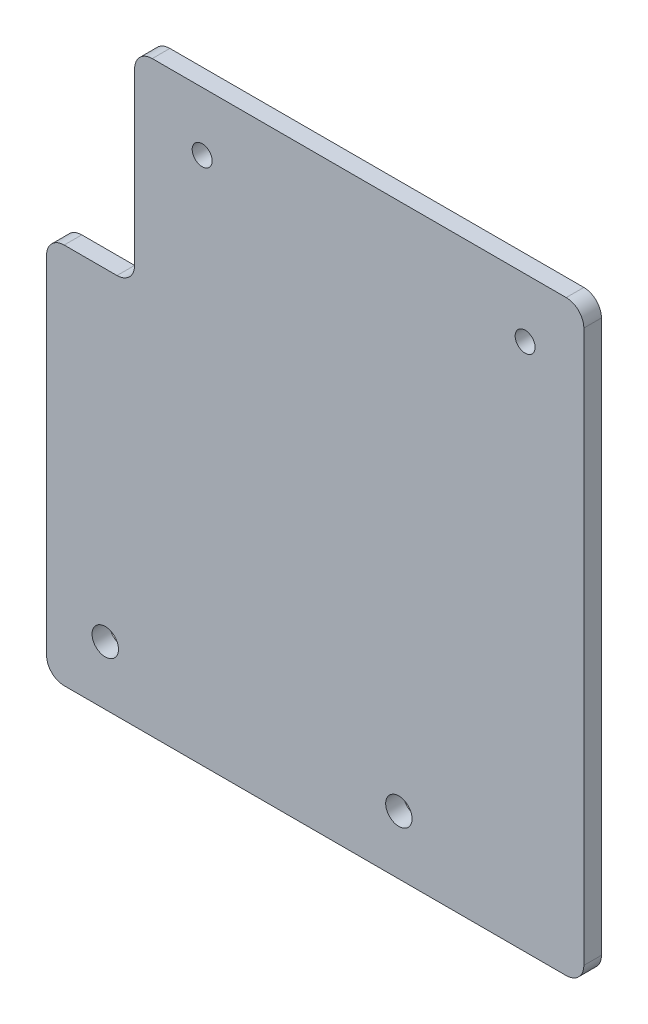
SolidWorks part; units mm, degrees
material "6061-T6 (SS)"
ref_plane "Front Plane" through (0, 0, 0) normal (0, 0, 1) x (1, 0, 0)
ref_plane "Top Plane" through (0, 0, 0) normal (0, 1, 0) x (1, 0, 0)
ref_plane "Right Plane" through (0, 0, 0) normal (1, 0, 0) x (0, 0, -1)
sketch "Sketch1" plane through (0, 0, 0) normal (0, 0, 1) x (1, 0, 0)
  line L0 (25, 0) -> (-25, 0) construction
  line L1 (-8.5, 0) -> (-8.5, 80) construction
  line L2 (-8.5, 80) -> (46.5, 80) construction
  line L4 (56.5, -10) -> (-35, -10)
  line L5 (56.5, -10) -> (56.5, 90)
  line L6 (56.5, 90) -> (-35, 90)
  line L7 (-35, -10) -> (-35, 90)
  line L8 (56.5, -10) -> (-35, 90) construction
  line L9 (56.5, 90) -> (-35, -10) construction
  point P4 (0, 0)
  point P7 (10.75, 40)
  dimension "D1" = 80
  dimension "D2" = 16.5
  dimension "D3" = 55
  dimension "D4" = 50
  dimension "D5" = 10
  dimension "D6" = 10
  dimension "D7" = 10
  dimension "D8" = 10
extrude "Boss-Extrude1" add sketch "Sketch1" along normal blind 3
hole_wizard "M4 Clearance Hole1" positions "Sketch2" profile "Sketch3" hole size "M4" standard "ANSI Metric" end condition through all
sketch "Sketch2" plane through (0, 0, 3) normal (0, 0, 1) x (1, 0, 0)
  point P0 (-25, 0)
  point P3 (25, 0)
sketch "Sketch3" plane through (-25, 0, 3) normal (1, 0, 0) x (0, -1, 0)
  line L0 (0, 0) -> (0, 3)
  line L1 (0, 3) -> (2.25, 3)
  line L2 (2.25, 3) -> (2.25, 0)
  line L5 (2.25, 0) -> (0, 0)
  line L11 (0, -6.35) -> (0, 107.95) construction
  dimension "Thru Hole Dia." = 4.5
  dimension "Thru Hole Depth" = 3
hole_wizard "M3 Clearance Hole1" positions "Sketch4" profile "Sketch5" hole size "M3" standard "ANSI Metric" end condition through all
sketch "Sketch4" plane through (0, 0, 3) normal (0, 0, 1) x (1, 0, 0)
  point P0 (-8.5, 80)
  point P3 (46.5, 80)
sketch "Sketch5" plane through (-8.5, 80, 3) normal (1, 0, 0) x (0, -1, 0)
  line L0 (0, 0) -> (0, 3)
  line L1 (0, 3) -> (1.7, 3)
  line L2 (1.7, 3) -> (1.7, 0)
  line L5 (1.7, 0) -> (0, 0)
  line L11 (0, -6.35) -> (0, 107.95) construction
  dimension "Thru Hole Dia." = 3.4
  dimension "Thru Hole Depth" = 3
sketch "Sketch6" plane through (0, 0, 3) normal (0, 0, 1) x (1, 0, 0)
  line L0 (56.5, 90) -> (-35, 90) construction
  line L1 (-20, 90) -> (-35, 90)
  line L2 (-20, 90) -> (-20, 55)
  line L3 (-20, 55) -> (-35, 55)
  line L4 (-35, 90) -> (-35, 55)
  line L5 (-35, 90) -> (-35, -10) construction
  dimension "D1" = 35
  dimension "D2" = 15
extrude "Cut-Extrude1" cut sketch "Sketch6" against normal through all
fillet "Fillet1" radius 3 6 edges at (56.5, 90, 1.5) (56.5, -10, 1.5) (-35, -10, 1.5) (-20, 90, 1.5) (-20, 55, 1.5) (-35, 55, 1.5)
